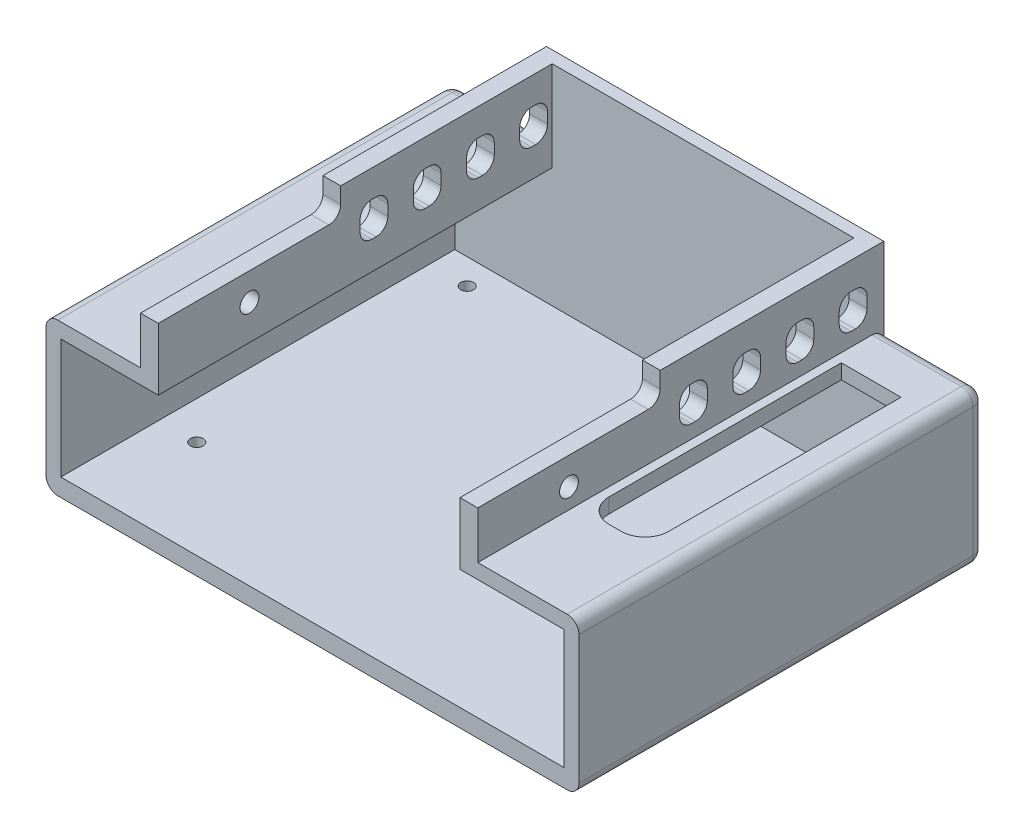
SolidWorks part; units mm, degrees
ref_plane "Front Plane" through (0, 0, 0) normal (0, 0, 1) x (1, 0, 0)
ref_plane "Top Plane" through (0, 0, 0) normal (0, 1, 0) x (1, 0, 0)
ref_plane "Right Plane" through (0, 0, 0) normal (1, 0, 0) x (0, 0, -1)
sketch "Sketch21" plane through (0, 0, 0) normal (0, 1, 0) x (1, 0, 0)
  circle A0 centre (-73.1204, 39.6354) radius 1.375
  circle A1 centre (12.8796, 39.6354) radius 1.375
  circle A2 centre (12.8796, -18.3646) radius 1.375
  circle A5 centre (-73.1204, -18.3646) radius 1.375
sketch "Sketch1" plane through (0, 0, 0) normal (0, 1, 0) x (1, 0, 0)
  line L1 (-84.4086, 47.6675) -> (29.8914, 47.6675)
  line L2 (-84.4086, 47.6675) -> (-84.4086, -39.4054)
  line L3 (-84.4086, -39.4054) -> (-81.2336, -39.4054)
  line L4 (29.8914, 47.6675) -> (29.8914, -39.4054)
  line L6 (-81.2336, 45.0817) -> (26.7164, 45.0817)
  line L7 (26.7164, 45.0817) -> (26.7164, -39.4054)
  line L8 (26.7164, -39.4054) -> (26.7164, 45.0817)
  line L9 (-81.2336, 45.0817) -> (-81.2336, -39.4054)
  line L10 (26.7164, -39.4054) -> (29.8914, -39.4054)
  point P4 (-27.2586, 45.0817)
  dimension "D1" = 3.175
  dimension "D2" = 3.175
  dimension "D3" = 107.95
extrude "Boss-Extrude2" add sketch "Sketch1" along normal blind 25.654 contours L7 L10 L4 L1 L2 L3 L9 L6 region at (-27.2586, 0, -46.2306)
sketch "Sketch11" plane through (0, 6.655, 0) normal (0, 1, 0) x (1, 0, 0)
  line L0 (10.0651, 36.6865) -> (22.8796, 36.6865)
  line L1 (22.8796, 36.6865) -> (22.8796, -18.229)
  line L2 (22.8796, -18.229) -> (10.0651, -18.229)
  line L3 (10.0651, -18.229) -> (10.0651, 36.6865)
  line L4 (-81.2336, 45.0817) -> (26.7164, 45.0817) construction
  line L5 (26.7164, 45.0817) -> (26.7164, -39.4054) construction
  dimension "D1" = 8.3952
  dimension "D2" = 3.8368
  dimension "D3" = 54.9155
  dimension "D4" = 12.8145
sketch "Sketch3" plane through (0, 25.654, 0) normal (0, 1, 0) x (1, 0, 0)
  line L0 (26.7164, -39.4054) -> (4.3796, -39.4054)
  line L1 (26.7164, -39.4054) -> (29.8914, -39.4054) construction
  line L2 (26.7164, 45.0817) -> (26.7164, -39.4054) construction
  line L4 (-81.2336, 45.0817) -> (-81.2336, -39.4054) construction
  line L6 (-81.2336, 45.0817) -> (26.7164, 45.0817) construction
  line L7 (-60.3318, 45.0817) -> (-60.3318, -0.0146)
  line L9 (4.3796, -0.0146) -> (4.3796, 45.0817)
  line L10 (4.3796, 45.0817) -> (26.7164, 45.0817)
  line L12 (-60.3318, -0.0146) -> (-60.3318, -39.4054)
  line L13 (-60.3318, -39.4054) -> (-60.3318, -0.0146)
  line L14 (4.3796, -0.0146) -> (4.3796, -39.4054)
  line L15 (4.3796, -39.4054) -> (4.3796, -0.0146)
  line L16 (-60.3318, -39.4054) -> (-78.5314, -39.4054)
  line L17 (-81.2336, 45.0817) -> (-81.2336, 47.6675)
  line L18 (-84.4086, 47.6675) -> (29.8914, 47.6675) construction
  line L19 (-81.2336, 47.6675) -> (26.7164, 47.6675)
  line L20 (26.7164, 47.6675) -> (26.7164, 45.0817)
  line L21 (-60.3318, 45.0817) -> (4.3796, 45.0817)
  line L22 (26.7164, 45.0817) -> (26.7164, 47.6675)
  line L23 (26.7164, 47.6675) -> (-81.2336, 47.6675)
  line L24 (-81.2336, 47.6675) -> (-84.4086, 47.6675)
  line L25 (-84.4086, 47.6675) -> (-84.4086, -39.4054)
  line L26 (-84.4086, 47.6675) -> (-84.4086, -39.4054) construction
  line L27 (-84.4086, -39.4054) -> (-60.3318, -39.4054)
  line L28 (26.7164, -39.4054) -> (29.8914, -39.4054)
  line L29 (29.8914, -39.4054) -> (29.8914, 47.6675)
  line L30 (29.8914, 47.6675) -> (29.8914, -39.4054) construction
  line L31 (29.8914, 47.6675) -> (26.7164, 47.6675)
  line M3 (26.7164, 45.0817) -> (26.7164, -39.4054)
  line M4 (26.7164, -39.4054) -> (29.8914, -39.4054)
  line M5 (29.8914, -39.4054) -> (29.8914, 47.6675)
  line M6 (29.8914, 47.6675) -> (-84.4086, 47.6675)
  line M7 (-84.4086, 47.6675) -> (-84.4086, -39.4054)
  line M8 (-84.4086, -39.4054) -> (-81.2336, -39.4054)
  line M9 (-81.2336, -39.4054) -> (-81.2336, 45.0817)
  line M10 (-81.2336, 45.0817) -> (26.7164, 45.0817)
extrude "Boss-Extrude4" add sketch "Sketch3" along normal blind 3.175 contours L16 L12 L7 M10 M9 | L17 M9 M6 M7 M8 | L20 L17 M6 M10 | L20 M6 M3 M4 M5 | L9 L14 L0 M3 M10 region at (28.3039, 25.654, -4.131) region at (15.548, 25.654, -2.8381) region at (-27.2586, 25.654, -46.3746) region at (-70.7827, 25.654, -2.8381) region at (-82.8211, 25.654, -4.131)
sketch "Sketch4" plane through (0, 28.829, 0) normal (0, 1, 0) x (1, 0, 0)
  line L0 (-64.1418, -0.2832) -> (-60.3318, -0.2832)
  line L1 (-60.3318, 45.0817) -> (-60.3318, -39.4054) construction
  line L2 (-60.3318, -0.2832) -> (-60.3318, 45.0817)
  line L3 (-60.3318, 45.0817) -> (4.3796, 45.0817)
  line L4 (-60.3318, 45.0817) -> (4.3796, 45.0817) construction
  line L5 (4.3796, 45.0817) -> (4.3796, -0.2832)
  line L6 (4.3796, -39.4054) -> (4.3796, 45.0817) construction
  line L7 (4.3796, -0.2832) -> (8.1896, -0.2832)
  line L8 (8.1896, -0.2832) -> (8.1896, 47.6675)
  line L9 (29.8914, 47.6675) -> (-84.4086, 47.6675) construction
  line L10 (8.1896, 47.6675) -> (-64.1418, 47.6675)
  line L11 (-64.1418, 47.6675) -> (-64.1418, -0.2832)
extrude "Boss-Extrude5" add sketch "Sketch4" along normal blind 16.1412
sketch "Sketch6" plane through (8.1896, 0, 0) normal (1, 0, 0) x (0, 0, -1)
  line L0 (-0.2832, 44.9702) -> (-0.2832, 28.829)
  line L1 (-0.2832, 44.9702) -> (-0.2832, 28.829) construction
  line L2 (-0.2832, 44.9702) -> (47.6675, 44.9702) construction
  line L3 (-39.4054, 28.829) -> (47.6675, 28.829) construction
  line L4 (-0.2832, 28.829) -> (2.9176, 28.829)
  line L5 (2.9176, 28.829) -> (2.9176, 44.9702)
  line L6 (2.9176, 44.9702) -> (-0.2832, 44.9702)
sketch "Sketch8" plane through (8.1896, 0, 0) normal (1, 0, 0) x (0, 0, -1)
  line L0 (44.0648, 39.1305) -> (44.0648, 31.7392)
  line L1 (44.0648, 31.7392) -> (38.1107, 31.7392)
  line L2 (38.1107, 31.7392) -> (38.1107, 39.1305)
  line L3 (38.1107, 39.1305) -> (44.0648, 39.1305)
  line L4 (26.6979, 39.1252) -> (32.652, 39.1252)
  line L5 (32.652, 39.1252) -> (32.652, 31.7339)
  line L6 (32.652, 31.7339) -> (26.6979, 31.7339)
  line L7 (26.6979, 31.7339) -> (26.6979, 39.1252)
  line L8 (15.2851, 39.1199) -> (21.2392, 39.1199)
  line L9 (21.2392, 39.1199) -> (21.2392, 31.7286)
  line L10 (21.2392, 31.7286) -> (15.2851, 31.7286)
  line L11 (15.2851, 31.7286) -> (15.2851, 39.1199)
  line L12 (3.8723, 39.1147) -> (9.8265, 39.1147)
  line L13 (9.8265, 39.1147) -> (9.8265, 31.7233)
  line L14 (9.8265, 31.7233) -> (3.8723, 31.7233)
  line L15 (3.8723, 31.7233) -> (3.8723, 39.1147)
  dimension "D1" = 4
extrude "Cut-Extrude1" cut sketch "Sketch8" against normal blind 99.314 and the other way blind 36.068 contours L8 L9 L10 L11
extrude "Cut-Extrude2" cut sketch "Sketch8<3>" against normal blind 99.314
sketch "Sketch8<3>" plane through (8.1896, 0, 0) normal (1, 0, 0) x (0, 0, -1) same geometry as "Sketch8"
sketch "Sketch10" plane through (0, 0, 0) normal (0, 1, 0) x (1, 0, 0)
  line L0 (-84.4086, 47.6675) -> (29.8914, 47.6675)
  line L1 (-84.4086, 47.6675) -> (-84.4086, -39.4054) construction
  line L2 (29.8914, -39.4054) -> (29.8914, 47.6675) construction
  line L3 (29.8914, 47.6675) -> (8.1896, 47.6675) construction
  line L4 (29.8914, 47.6675) -> (29.8914, -39.4054)
  line L5 (29.8914, -39.4054) -> (4.3796, -39.4054) construction
  line L6 (29.8914, -39.4054) -> (-84.4086, -39.4054)
  line L7 (-84.4086, -39.4054) -> (-84.4086, 47.6675)
extrude "Boss-Extrude7" add sketch "Sketch10" against normal blind 3.81
extrude "Cut-Extrude4" cut sketch "Sketch11" along normal blind 23.368
sketch "Sketch18" plane through (0, 28.829, 0) normal (0, 1, 0) x (1, 0, 0)
  line L0 (-60.3318, -0.2832) -> (-60.3318, -39.4054) construction
  line L1 (-60.3318, -39.4054) -> (-64.1418, -39.4054)
  line L2 (-60.3318, -39.4054) -> (-60.3318, -0.2832)
  line L3 (-60.3318, -0.2832) -> (-64.1418, -0.2832)
  line L4 (-64.1418, -39.4054) -> (-64.1418, -0.2832)
  line L5 (-84.4086, -39.4054) -> (-60.3318, -39.4054) construction
  line L6 (-64.1418, -0.2832) -> (-60.3318, -0.2832) construction
  line L7 (29.8914, -39.4054) -> (4.3796, -39.4054) construction
  line L8 (8.1896, -39.4054) -> (4.3796, -39.4054)
  line L9 (8.1896, -39.4054) -> (8.1896, -0.2832)
  line L10 (8.1896, -0.2832) -> (4.3796, -0.2832)
  line L11 (4.3796, -39.4054) -> (4.3796, -0.2832)
  line L12 (4.3796, -39.4054) -> (4.3796, -0.2832) construction
  line L13 (4.3796, 45.0817) -> (4.3796, -0.2832) construction
extrude "Boss-Extrude10" add sketch "Sketch18" along normal blind 10.16 contours L11 L10 L9 L8 | L4 L3 L2 L1
sketch "Sketch20" plane through (8.1896, 0, 0) normal (1, 0, 0) x (0, 0, -1)
  line L0 (-19.8443, 38.989) -> (-19.8443, 28.829)
  line L1 (-39.4054, 38.989) -> (-0.2832, 38.989) construction
  line L2 (-39.4054, 28.829) -> (47.6675, 28.829) construction
  circle A2 centre (-19.8443, 33.1259) radius 2.0193
  dimension "D3" = 4.0386
extrude "Cut-Extrude5" cut sketch "Sketch20" against normal blind 93.218 and the other way blind 33.528 contours A2
extrude "Cut-Extrude7" cut sketch "Sketch21" against normal up to next
fillet "Fillet1" radius 2.54 9 edges at (19.0405, 28.829, -47.6675) (29.8914, 28.829, -4.131) (-84.4086, -3.81, -4.131) (-84.4086, 12.5095, -47.6675) (29.8914, 12.5095, -47.6675) (-27.2586, -3.81, -47.6675) (29.8914, -3.81, -4.131) (-84.4086, 28.829, -4.131) (-74.2752, 28.829, -47.6675)
fillet "Fillet2" radius 2.54 32 edges at (-62.2368, 39.1199, -21.2392) (-62.2368, 31.7286, -21.2392) (-62.2368, 31.7286, -15.2851) (-62.2368, 39.1199, -15.2851) (-62.2368, 31.7233, -3.8723) (-62.2368, 39.1147, -3.8723) (-62.2368, 39.1147, -9.8265) (-62.2368, 31.7233, -9.8265) (-62.2368, 31.7339, -26.6979) (-62.2368, 39.1252, -26.6979) (-62.2368, 39.1252, -32.652) (-62.2368, 31.7339, -32.652) (-62.2368, 31.7392, -38.1107) (-62.2368, 39.1305, -38.1107) (-62.2368, 39.1305, -44.0648) (-62.2368, 31.7392, -44.0648) (6.2846, 39.1199, -15.2851) (6.2846, 39.1199, -21.2392) (6.2846, 31.7286, -21.2392) (6.2846, 31.7286, -15.2851) (6.2846, 31.7233, -9.8265) (6.2846, 39.1147, -3.8723) (6.2846, 39.1147, -9.8265) (6.2846, 31.7339, -32.652) (6.2846, 31.7339, -26.6979) (6.2846, 39.1252, -26.6979) (6.2846, 39.1252, -32.652) (6.2846, 39.1305, -44.0648) (6.2846, 31.7392, -44.0648) (6.2846, 31.7392, -38.1107) (6.2846, 39.1305, -38.1107) (6.2846, 31.7233, -3.8723)
fillet "Fillet3" radius 2.54 2 edges at (-62.2368, 38.989, 0.2832) (6.2846, 38.989, 0.2832)
fillet "Fillet4" radius 5.08 2 edges at (10.0651, 27.2415, 18.229) (22.8796, 27.2415, 18.229)
